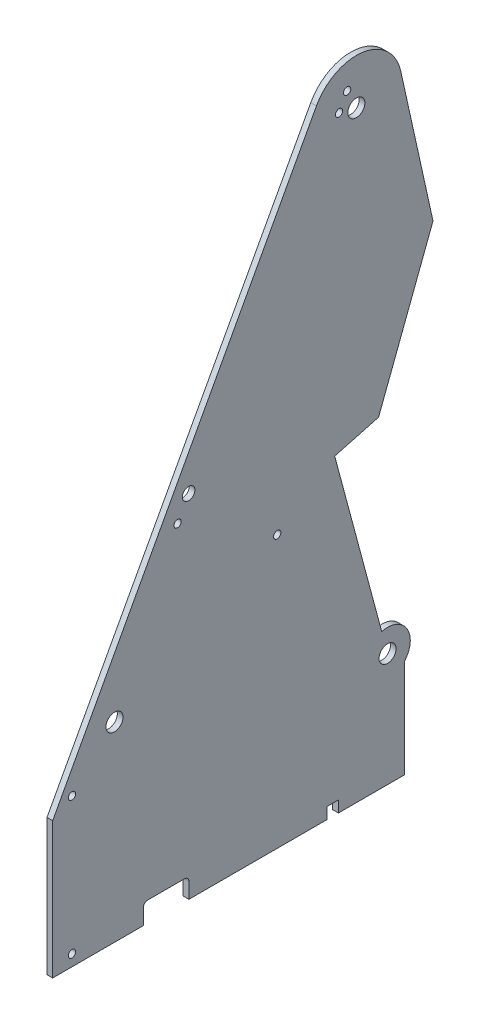
SolidWorks part; units mm, degrees
ref_plane "Front Plane" through (0, 0, 0) normal (0, 0, 1) x (1, 0, 0)
ref_plane "Top Plane" through (0, 0, 0) normal (0, 1, 0) x (1, 0, 0)
ref_plane "Right Plane" through (0, 0, 0) normal (1, 0, 0) x (0, 0, -1)
sketch "Sketch1" plane through (0, 0, 0) normal (1, 0, 0) x (0, 0, -1)
  line L0 (0, 0) -> (0, 55.0997)
  line L6 (-39.108, 173.9053) -> (-14.5735, 180.4793)
  line L7 (-14.5735, 180.4793) -> (15.875, 260.35)
  line L8 (15.875, 260.35) -> (-2.1865, 342.0339)
  line L9 (-49.3231, 348.6446) -> (-196.85, 76.2)
  line L10 (-196.85, 0) -> (0, 0)
  line L11 (-196.85, 76.2) -> (-196.85, 0)
  line L13 (-39.108, 173.9053) -> (-12.812, 75.7673)
  line L14 (-12.812, 75.7673) -> (13.738, 82.8813) construction
  arc A0 (-2.1865, 342.0339) -> (-49.3231, 348.6446) centre (-26.9875, 336.55) ccw
  arc A3 (0, 55.0997) -> (-12.812, 75.7673) centre (-9.525, 63.5) ccw
  dimension "D2" = 25.4
  dimension "D6" = 196.85
  dimension "D7" = 76.2
  dimension "D12" = 12.7
  dimension "D1" = 26.9875
  dimension "D3" = 336.55
  dimension "D4" = 25.4
  dimension "D5" = 101.6
  dimension "D10" = 9.525
  dimension "D11" = 63.5
  dimension "D13" = 76.2
  dimension "D14" = 15.875
  dimension "D15" = 15
extrude "Boss-Extrude1" add sketch "Sketch1" along normal blind 3.175
sketch "Sketch2" plane through (3.175, 0, 0) normal (1, 0, 0) x (0, 0, -1)
  line L16 (-146.05, 8.7909) -> (-146.05, -0.3034) construction
  line L17 (-123.0376, 11.1785) -> (-143.6624, 11.1785) construction
  line L18 (-120.65, -0.3034) -> (-120.65, 8.7909) construction
  line L19 (-146.05, 8.7909) -> (-146.05, 0)
  line L20 (-123.0376, 11.1785) -> (-143.6624, 11.1785)
  line L21 (-120.65, 0) -> (-120.65, 8.7909)
  line L23 (-37.0504, 0) -> (-37.0504, 6.35) construction
  line L24 (-43.4004, 0) -> (-37.0504, 0) construction
  line L25 (-146.05, 0) -> (-120.65, 0)
  line L26 (-196.85, 0) -> (0, 0) construction
  line L27 (-43.4004, 6.35) -> (-43.4004, 0) construction
  line L28 (-37.0504, 6.35) -> (-43.4004, 6.35) construction
  line L29 (-37.0504, 0) -> (-37.0504, 6.35)
  line L30 (-43.4004, 0) -> (-37.0504, 0)
  line L31 (-43.4004, 6.35) -> (-43.4004, 0)
  line L32 (-37.0504, 6.35) -> (-43.4004, 6.35)
  line L33 (-223.2996, 0) -> (-223.2996, 6.35) construction
  line L34 (-229.6496, 0) -> (-223.2996, 0) construction
  line L35 (-229.6496, 6.35) -> (-229.6496, 0) construction
  line L36 (-223.2996, 6.35) -> (-229.6496, 6.35) construction
  line L37 (-223.2996, 0) -> (-223.2996, 6.35)
  line L38 (-229.6496, 0) -> (-223.2996, 0)
  line L39 (-229.6496, 6.35) -> (-229.6496, 0)
  line L40 (-223.2996, 6.35) -> (-229.6496, 6.35)
  arc A0 (-143.6624, 11.1785) -> (-146.05, 8.7909) centre (-143.6624, 8.7909) ccw construction
  arc A1 (-120.65, 8.7909) -> (-123.0376, 11.1785) centre (-123.0376, 8.7909) ccw construction
  arc A2 (-143.6624, 11.1785) -> (-146.05, 8.7909) centre (-143.6624, 8.7909) ccw
  arc A3 (-120.65, 8.7909) -> (-123.0376, 11.1785) centre (-123.0376, 8.7909) ccw
extrude "Cut-Extrude1" cut sketch "Sketch2" against normal through all
sketch "Sketch3" plane through (3.175, 0, 0) normal (1, 0, 0) x (0, 0, -1)
  point P0 (-26.9875, 336.55)
  point P4 (-9.525, 63.5)
hole_wizard "3/8 Clearance Hole1" positions "Sketch3" profile "Sketch4" hole size "3/8" standard "ANSI Inch" end condition up to next
sketch "Sketch4" plane through (3.175, 336.55, 26.9875) normal (0, 1, 0) x (0, 0, -1)
  line L0 (0, 0) -> (0, 3.175)
  line L1 (0, 3.175) -> (4.7625, 3.175)
  line L2 (4.7625, 3.175) -> (4.7625, 0)
  line L5 (4.7625, 0) -> (0, 0)
  line L11 (0, -6.35) -> (0, 107.95) construction
  dimension "Thru Hole Dia." = 9.525
  dimension "Thru Hole Depth" = 3.175
sketch "Sketch5" plane through (3.175, 0, 0) normal (1, 0, 0) x (0, 0, -1)
  line L0 (-9.525, 63.5) -> (26.2895, 27.4728)
  line L1 (26.2895, 27.4728) -> (26.2524, 14.9296)
  line L2 (21.8127, 31.9762) -> (-24.8224, 22.3166)
  line L3 (-15.875, 19.05) -> (-24.8224, 22.3166)
  line L4 (0, 0) -> (0, 55.0997) construction
  line L5 (-15.875, 19.05) -> (-33.1481, 11.0161)
  line L6 (-33.1481, 11.0161) -> (-54.7505, 169.5016)
  line L7 (50.8, 0) -> (50.8, 73.5762) construction
  dimension "D1" = 44.45
  dimension "D2" = 50.8
  dimension "D3" = 45
  dimension "D4" = 60.325
  dimension "D5" = 19.05
  dimension "D6" = 15.875
  dimension "D7" = 9.525
  dimension "D8" = 47.625
  dimension "D9" = 19.05
  dimension "D10" = 45
  dimension "D11" = 50.8
sketch "Sketch6" plane through (3.175, 0, 0) normal (1, 0, 0) x (0, 0, -1)
  line L1 (-162.2756, 106.7109) -> (-176.2354, 114.27) construction
  line L3 (-49.3231, 348.6446) -> (-196.85, 76.2) construction
  circle A2 centre (-162.2756, 106.7109) radius 4.7625
  dimension "D4" = 9.525
  dimension "D5" = 15.875
  dimension "D6" = 266.7
extrude "Cut-Extrude2" cut sketch "Sketch6" against normal through all
sketch "Sketch8" [suppressed] plane through (3.175, 0, 0) normal (1, 0, 0) x (0, 0, -1)
  circle A0 centre (-161.5793, 82.5968) radius 4.7625
  circle A1 centre (-175.4929, 67.6784) radius 2.032
  circle A2 centre (-121.6449, 97.1424) radius 2.032
  circle A3 centre (-175.4929, 67.6784) radius 1.905 construction
  circle A4 centre (-121.6449, 97.1424) radius 1.985 construction
  dimension "D1" = 25.4
  dimension "D2" = 9.525
  dimension "D3" = 4.064
extrude "Cut-Extrude3" [suppressed] cut sketch "Sketch8" against normal through all both and the other way through all
sketch "Sketch9" [suppressed] plane through (3.175, 0, 0) normal (1, 0, 0) x (0, 0, -1)
  circle A8 centre (-175.4929, 67.6784) radius 4.445
  circle A9 centre (-175.4929, 67.6784) radius 4.445
  dimension "D1" = 2.54
sketch "Sketch10" plane through (3.175, 0, 0) normal (1, 0, 0) x (0, 0, -1)
  circle A0 centre (-71.2566, 151.9429) radius 2.032
  dimension "D1" = 4.064
extrude "Cut-Extrude4" cut sketch "Sketch10" against normal through all
sketch "Sketch11" plane through (3.175, 0, 0) normal (1, 0, 0) x (0, 0, -1)
  circle A0 centre (-186.055, 82.7999) radius 2.032
  circle A1 centre (-186.055, 6.35) radius 2.032
  circle A2 centre (-186.055, 6.35) radius 2.032 construction
  circle A3 centre (-186.055, 82.7999) radius 2.032 construction
  dimension "D1" = 4.064
extrude "Cut-Extrude5" cut sketch "Sketch11" against normal through all
sketch "Sketch13" plane through (0, 0, 0) normal (-1, 0, 0) x (0, 0, 1)
  circle A0 centre (32.145, 347.3369) radius 2.032
  circle A1 centre (36.6805, 338.961) radius 2.032
  dimension "D1" = 4.064
extrude "Cut-Extrude6" cut sketch "Sketch13" against normal through all
sketch "Sketch14" plane through (3.175, 0, 0) normal (1, 0, 0) x (0, 0, -1)
  line L0 (-49.3231, 348.6446) -> (-196.85, 76.2) construction
  line L1 (-127, 185.1916) -> (-135.3759, 189.7271) construction
  circle A0 centre (-127, 185.1916) radius 2.032
  dimension "D1" = 4.064
  dimension "D2" = 9.525
  dimension "D3" = 127
extrude "Cut-Extrude7" cut sketch "Sketch14" against normal through all
sketch "Sketch15" plane through (3.175, 0, 0) normal (1, 0, 0) x (0, 0, -1)
  circle A0 centre (-120.8099, 196.6232) radius 3.4925
  circle A2 centre (-120.8099, 196.6232) radius 2.415 construction
  dimension "D1" = 6.985
extrude "Cut-Extrude8" cut sketch "Sketch15" against normal through all
